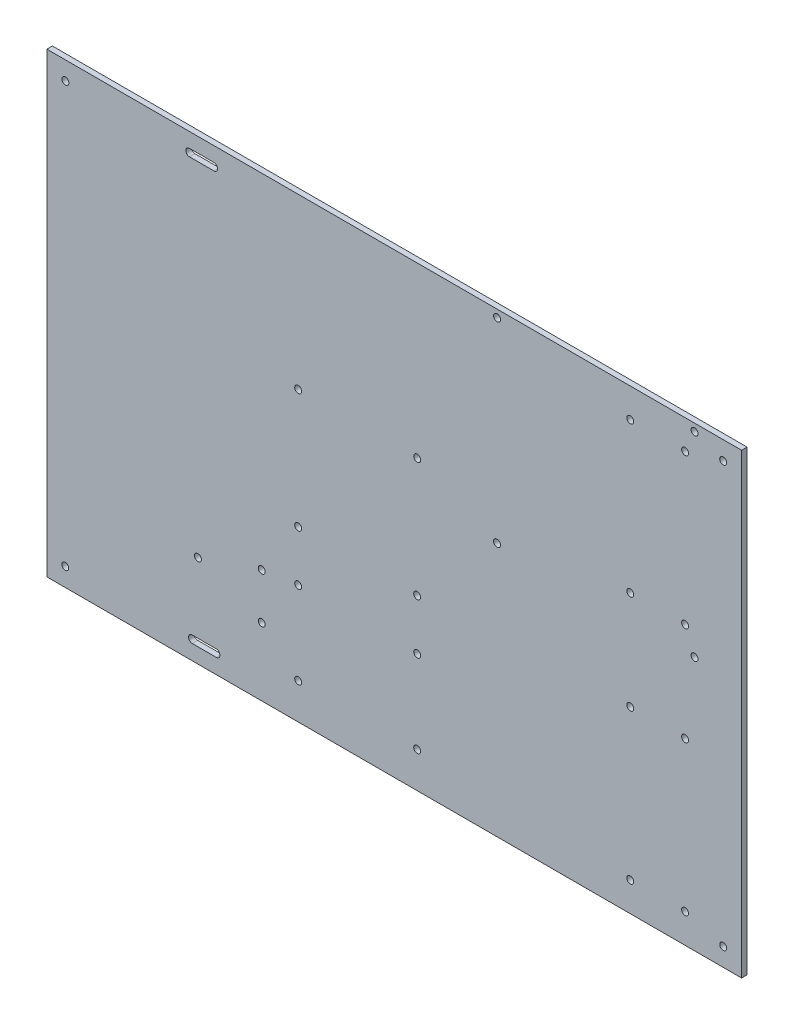
SolidWorks part; units mm, degrees
note: '?' marks a value the reader was unsure of.
ref_plane "Front Plane" through (0, 0, 0) normal (0, 0, 1) x (1, 0, 0)
ref_plane "Top Plane" through (0, 0, 0) normal (0, 1, 0) x (1, 0, 0)
ref_plane "Right Plane" through (0, 0, 0) normal (1, 0, 0) x (0, 0, -1)
sketch "Sketch1" plane through (0, 0, 0) normal (0, 0, 1) x (1, 0, 0)
  line L0 (190, 125) -> (-190, -125) construction
  line L1 (-190, 125) -> (190, 125)
  line L2 (-190, 125) -> (-190, -125)
  line L3 (-190, -125) -> (190, -125)
  line L4 (190, 125) -> (190, -125)
  point P4 (0, 0)
  dimension "D1" = 380
  dimension "D2" = 250
base flange "Base-Flange2" sketch "Sketch1" thickness 3 reverse thickness direction no parameters "D1"=3
hole_wizard "#25 (0.1495) Diameter Slot1" positions "Sketch16" profile "Sketch15" size "#25" standard "ANSI Inch" slot yes end condition through all
sketch "Sketch16" plane through (0, 0, 0) normal (0, 0, 1) x (1, 0, 0)
  point P0 (179.9298, 114.9245)
sketch "Sketch15" plane through (179.9298, 114.9245, 0) normal (1, 0, 0) x (0, -1, 0)
  line L0 (0, 0) -> (0, 3)
  line L1 (0, 3) -> (1.8986, 3)
  line L2 (1.8986, 3) -> (1.8986, 0)
  line L5 (1.8986, 0) -> (0, 0)
  line L11 (0, -6.35) -> (0, 107.95) construction
  dimension "Thru Hole Dia." = 3.7973
  dimension "Thru Hole Depth" = 3
hole_wizard "#25 (0.1495) Diameter Slot2" positions "Sketch18" profile "Sketch17" size "#25" standard "ANSI Inch" slot yes end condition through all
sketch "Sketch18" plane through (0, 0, 0) normal (0, 0, 1) x (1, 0, 0)
  point P0 (179.9396, -115.0634)
sketch "Sketch17" plane through (179.9396, -115.0634, 0) normal (1, 0, 0) x (0, -1, 0)
  line L0 (0, 0) -> (0, 3)
  line L1 (0, 3) -> (1.8986, 3)
  line L2 (1.8986, 3) -> (1.8986, 0)
  line L5 (1.8986, 0) -> (0, 0)
  line L11 (0, -6.35) -> (0, 107.95) construction
  dimension "Thru Hole Dia." = 3.7973
  dimension "Thru Hole Depth" = 3
hole_wizard "#25 (0.1495) Diameter Slot3" positions "Sketch20" profile "Sketch19" size "#25" standard "ANSI Inch" slot yes end condition through all
sketch "Sketch20" plane through (0, 0, 0) normal (0, 0, 1) x (1, 0, 0)
  point P0 (-179.9606, -114.9497)
sketch "Sketch19" plane through (-179.9606, -114.9497, 0) normal (1, 0, 0) x (0, -1, 0)
  line L0 (0, 0) -> (0, 3)
  line L1 (0, 3) -> (1.8986, 3)
  line L2 (1.8986, 3) -> (1.8986, 0)
  line L5 (1.8986, 0) -> (0, 0)
  line L11 (0, -6.35) -> (0, 107.95) construction
  dimension "Thru Hole Dia." = 3.7973
  dimension "Thru Hole Depth" = 3
hole_wizard "#25 (0.1495) Diameter Slot4" positions "Sketch24" profile "Sketch23" size "#25" standard "ANSI Inch" slot yes end condition through all
sketch "Sketch24" plane through (0, 0, 0) normal (0, 0, 1) x (1, 0, 0)
  point P0 (-179.8929, 115.0122)
sketch "Sketch23" plane through (-179.8929, 115.0122, 0) normal (1, 0, 0) x (0, -1, 0)
  line L0 (0, 0) -> (0, 3)
  line L1 (0, 3) -> (1.8986, 3)
  line L2 (1.8986, 3) -> (1.8986, 0)
  line L5 (1.8986, 0) -> (0, 0)
  line L11 (0, -6.35) -> (0, 107.95) construction
  dimension "Thru Hole Dia." = 3.7973
  dimension "Thru Hole Depth" = 3
sketch "Sketch26" plane through (0, 0, 0) normal (0, 1, 0) x (1, 0, 0)
  line L0 (0, 0) -> (0, 26.1192) construction
ref_axis "Axis1" through (0, 0, 65.499) along (0, 0, -1)?
hole_wizard "#25 (0.1495) Diameter Slot5" positions "Sketch33" profile "Sketch31" size "#25" standard "ANSI Inch" slot yes end condition through all
sketch "Sketch33" plane through (0, 0, 0) normal (0, 0, 1) x (1, 0, 0)
  point P0 (-52.5501, 32.5501)
  point P6 (-52.5501, -32.5501)
  point P9 (12.5501, -32.5501)
  point P12 (12.5501, 32.5501)
sketch "Sketch31" plane through (-52.5501, 32.5501, 0) normal (1, 0, 0) x (0, -1, 0)
  line L0 (0, 0) -> (0, 3)
  line L1 (0, 3) -> (1.8986, 3)
  line L2 (1.8986, 3) -> (1.8986, 0)
  line L5 (1.8986, 0) -> (0, 0)
  line L11 (0, -6.35) -> (0, 107.95) construction
  dimension "Thru Hole Dia." = 3.7973
  dimension "Thru Hole Depth" = 3
hole_wizard "#25 (0.1495) Diameter Slot6" positions "Sketch35" profile "Sketch34" size "#25" standard "ANSI Inch" slot yes end condition through all
sketch "Sketch35" plane through (0, 0, 0) normal (0, 0, 1) x (1, 0, 0)
  point P0 (-107.3842, -74.5316)
  point P3 (-72.5, -87.9216)
  point P6 (-72.5, -62.9216)
sketch "Sketch34" plane through (-107.3842, -74.5316, 0) normal (1, 0, 0) x (0, -1, 0)
  line L0 (0, 0) -> (0, 3)
  line L1 (0, 3) -> (1.8986, 3)
  line L2 (1.8986, 3) -> (1.8986, 0)
  line L5 (1.8986, 0) -> (0, 0)
  line L11 (0, -6.35) -> (0, 107.95) construction
  dimension "Thru Hole Dia." = 3.7973
  dimension "Thru Hole Depth" = 3
hole_wizard "#25 (0.1495) Diameter Slot8" positions "Sketch39" profile "Sketch38" size "#25" standard "ANSI Inch" slot yes end condition through all
sketch "Sketch39" plane through (0, 0, 0) normal (0, 0, 1) x (1, 0, 0)
  point P0 (164.2422, 120.9)
  point P3 (56.2422, 120.9)
  point P6 (56.2422, 14.1)
  point P9 (164.2422, 14.1)
sketch "Sketch38" plane through (164.2422, 120.9, 0) normal (1, 0, 0) x (0, -1, 0)
  line L0 (0, 0) -> (0, 3)
  line L1 (0, 3) -> (1.8986, 3)
  line L2 (1.8986, 3) -> (1.8986, 0)
  line L5 (1.8986, 0) -> (0, 0)
  line L11 (0, -6.35) -> (0, 107.95) construction
  dimension "Thru Hole Dia." = 3.7973
  dimension "Thru Hole Depth" = 3
hole_wizard "#25 (0.1495) Diameter Slot9" positions "Sketch41" profile "Sketch40" size "#25" standard "ANSI Inch" slot yes end condition through all
sketch "Sketch41" plane through (0, 0, 0) normal (0, 0, 1) x (1, 0, 0)
  point P0 (-52.5501, -105.4405)
  point P4 (12.5501, -60.1655)
  point P6 (-52.5501, -60.1655)
sketch "Sketch40" plane through (-52.5501, -105.4405, 0) normal (1, 0, 0) x (0, -1, 0)
  line L0 (0, 0) -> (0, 3)
  line L1 (0, 3) -> (1.8986, 3)
  line L2 (1.8986, 3) -> (1.8986, 0)
  line L5 (1.8986, 0) -> (0, 0)
  line L11 (0, -6.35) -> (0, 107.95) construction
  dimension "Thru Hole Dia." = 3.7973
  dimension "Thru Hole Depth" = 3
hole_wizard "#25 (0.1495) Diameter Slot10" positions "Sketch43" profile "Sketch42" size "#25" standard "ANSI Inch" slot yes end condition through all
sketch "Sketch43" plane through (0, 0, 0) normal (0, 0, 1) x (1, 0, 0)
  point P0 (12.5501, -105.4405)
sketch "Sketch42" plane through (12.5501, -105.4405, 0) normal (1, 0, 0) x (0, -1, 0)
  line L0 (0, 0) -> (0, 3)
  line L1 (0, 3) -> (1.8986, 3)
  line L2 (1.8986, 3) -> (1.8986, 0)
  line L5 (1.8986, 0) -> (0, 0)
  line L11 (0, -6.35) -> (0, 107.95) construction
  dimension "Thru Hole Dia." = 3.7973
  dimension "Thru Hole Depth" = 3
sketch "Sketch44" plane through (0, 0, 0) normal (0, 0, 1) x (1, 0, 0)
  line L0 (-110.5183, -114.787) -> (-97.3506, -114.787) construction
  line L1 (-110.5183, -125) -> (-110.5183, 125) construction
  line L2 (-97.3506, -122) -> (-97.3506, -98) construction
  line L3 (-110.5183, -112.787) -> (-97.3506, -112.787)
  line L4 (-110.5183, -116.787) -> (-97.3506, -116.787)
  arc A0 (-110.5183, -112.787) -> (-110.5183, -116.787) centre (-110.5183, -114.787) ccw
  arc A1 (-97.3506, -116.787) -> (-97.3506, -112.787) centre (-97.3506, -114.787) ccw
  point P6 (-103.9345, -114.787)
extrude "Cut-Extrude1" cut sketch "Sketch44" against normal blind 10
sketch "Sketch45" plane through (0, 0, 0) normal (0, 0, 1) x (1, 0, 0)
  line L0 (-112.0183, 115) -> (-98.6238, 115) construction
  line L3 (-112.0183, -125) -> (-112.0183, 125) construction
  line L4 (-98.6238, 125) -> (-98.6238, -125) construction
  line L5 (-112.0183, 117) -> (-98.6238, 117)
  line L6 (-112.0183, 113) -> (-98.6238, 113)
  arc A0 (-112.0183, 117) -> (-112.0183, 113) centre (-112.0183, 115) ccw
  arc A1 (-98.6238, 113) -> (-98.6238, 117) centre (-98.6238, 115) ccw
  point P7 (-105.321, 115)
extrude "Cut-Extrude2" cut sketch "Sketch45" against normal blind 10
hole_wizard "#25 (0.1495) Diameter Slot11" positions "Sketch47" profile "Sketch46" size "#25" standard "ANSI Inch" slot yes end condition through all
sketch "Sketch47" plane through (0, 0, -3) normal (0, 0, -1) x (-1, 0, 0)
  point P0 (-129.0851, -27)
  point P3 (-159.0851, -27)
  point P6 (-159.0851, -109)
  point P9 (-129.0851, -109)
  point P12 (-159.0851, 27)
  point P15 (-129.0851, 27)
  point P18 (-159.0851, 109)
  point P21 (-129.0851, 109)
sketch "Sketch46" plane through (129.0851, -27, -3) normal (1, 0, 0) x (0, 1, 0)
  line L0 (0, 0) -> (0, 3)
  line L1 (0, 3) -> (1.8986, 3)
  line L2 (1.8986, 3) -> (1.8986, 0)
  line L5 (1.8986, 0) -> (0, 0)
  line L11 (0, -6.35) -> (0, 107.95) construction
  dimension "Thru Hole Dia." = 3.7973
  dimension "Thru Hole Depth" = 3
sketch "Bend-Lines3" plane through (0, 0, 0) normal (0, 1, 0) x (1, 0, 0)
sketch "Bounding-Box3" plane through (0, 0, 0) normal (0, 1, 0) x (1, 0, 0)
sheet metal parameters "Sheet-Metal2" thickness 3 parameters "D1"=3
flat pattern "Flat-Pattern2" [suppressed]
sketch "Bend-Lines4" plane through (0, 0, 0) normal (0, 1, 0) x (1, 0, 0)
sketch "Bounding-Box4" [suppressed] plane through (0, 0, 0) normal (0, 1, 0) x (1, 0, 0)
sheet metal parameters "Sheet-Metal5" thickness 3 parameters "D1"=3
flat pattern "Flat-Pattern2" [suppressed]
sketch "Bend-Lines4" plane through (0, 0, 0) normal (0, 1, 0) x (1, 0, 0)
sketch "Bounding-Box4" [suppressed] plane through (0, 0, 0) normal (0, 1, 0) x (1, 0, 0)
sheet metal parameters "Sheet-Metal6" thickness 3 parameters "D1"=3
flat pattern "Flat-Pattern2" [suppressed]
sketch "Bend-Lines4" plane through (0, 0, 0) normal (0, 1, 0) x (1, 0, 0)
sketch "Bounding-Box4" [suppressed] plane through (0, 0, 0) normal (0, 1, 0) x (1, 0, 0)
sheet metal parameters "Sheet-Metal7" thickness 3 parameters "D1"=3
flat pattern "Flat-Pattern2" [suppressed]
sketch "Bend-Lines4" plane through (0, 0, 0) normal (0, 1, 0) x (1, 0, 0)
sketch "Bounding-Box4" [suppressed] plane through (0, 0, 0) normal (0, 1, 0) x (1, 0, 0)
sheet metal parameters "Sheet-Metal8" thickness 3 parameters "D1"=3
flat pattern "Flat-Pattern2" [suppressed]
sketch "Bend-Lines4" plane through (0, 0, 0) normal (0, 1, 0) x (1, 0, 0)
sketch "Bounding-Box4" [suppressed] plane through (0, 0, 0) normal (0, 1, 0) x (1, 0, 0)
sheet metal parameters "Sheet-Metal12" thickness 3 parameters "D1"=3
flat pattern "Flat-Pattern2" [suppressed]
sketch "Bend-Lines4" plane through (0, 0, 0) normal (0, 1, 0) x (1, 0, 0)
sketch "Bounding-Box4" [suppressed] plane through (0, 0, 0) normal (0, 1, 0) x (1, 0, 0)
sheet metal parameters "Sheet-Metal13" thickness 3 parameters "D1"=3
flat pattern "Flat-Pattern2" [suppressed]
sketch "Bend-Lines4" plane through (0, 0, 0) normal (0, 1, 0) x (1, 0, 0)
sketch "Bounding-Box4" [suppressed] plane through (0, 0, 0) normal (0, 1, 0) x (1, 0, 0)
sheet metal parameters "Sheet-Metal15" thickness 3 parameters "D1"=3
flat pattern "Flat-Pattern2" [suppressed]
sketch "Bend-Lines4" plane through (0, 0, 0) normal (0, 1, 0) x (1, 0, 0)
sketch "Bounding-Box4" [suppressed] plane through (0, 0, 0) normal (0, 1, 0) x (1, 0, 0)
sheet metal parameters "Sheet-Metal16" thickness 3 parameters "D1"=3
flat pattern "Flat-Pattern2" [suppressed]
sketch "Bend-Lines4" plane through (0, 0, 0) normal (0, 1, 0) x (1, 0, 0)
sketch "Bounding-Box4" [suppressed] plane through (0, 0, 0) normal (0, 1, 0) x (1, 0, 0)
sheet metal parameters "Sheet-Metal17" thickness 3 parameters "D1"=3
flat pattern "Flat-Pattern2" [suppressed]
sketch "Bend-Lines4" plane through (0, 0, 0) normal (0, 1, 0) x (1, 0, 0)
sketch "Bounding-Box4" [suppressed] plane through (0, 0, 0) normal (0, 1, 0) x (1, 0, 0)
sheet metal parameters "Sheet-Metal18" thickness 3 parameters "D1"=3
flat pattern "Flat-Pattern2" [suppressed]
sketch "Bend-Lines4" plane through (0, 0, 0) normal (0, 1, 0) x (1, 0, 0)
sketch "Bounding-Box4" [suppressed] plane through (0, 0, 0) normal (0, 1, 0) x (1, 0, 0)
sheet metal parameters "Sheet-Metal19" thickness 3 parameters "D1"=3
flat pattern "Flat-Pattern2" [suppressed]
sketch "Bend-Lines4" plane through (0, 0, 0) normal (0, 1, 0) x (1, 0, 0)
sketch "Bounding-Box4" [suppressed] plane through (0, 0, 0) normal (0, 1, 0) x (1, 0, 0)
sheet metal parameters "Sheet-Metal21" thickness 3 parameters "D1"=3
flat pattern "Flat-Pattern2" [suppressed]
sketch "Bend-Lines4" plane through (0, 0, 0) normal (0, 1, 0) x (1, 0, 0)
sketch "Bounding-Box4" [suppressed] plane through (0, 0, 0) normal (0, 1, 0) x (1, 0, 0)
